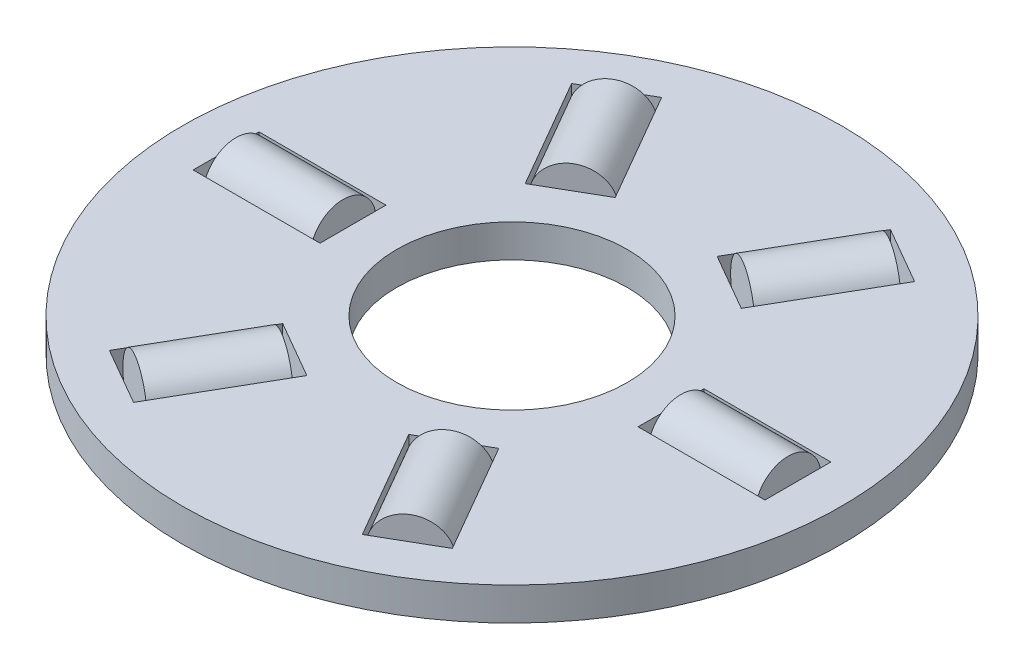
SolidWorks part; units mm, degrees
ref_plane "前视基准面" through (0, 0, 0) normal (0, 0, 1) x (1, 0, 0)
ref_plane "上视基准面" through (0, 0, 0) normal (0, 1, 0) x (1, 0, 0)
ref_plane "右视基准面" through (0, 0, 0) normal (1, 0, 0) x (0, 0, -1)
sketch "草图1" plane through (0, 0, 0) normal (0, 0, 1) x (1, 0, 0)
  line L0 (0, 87.2061) -> (0, -91.5733) construction
  line L1 (-94.3327, 0) -> (80.3525, 0) construction
  line L2 (-3.5, 0.5) -> (-3.5, -0.5)
  line L3 (-10, 0.5) -> (-3.5, 0.5)
  line L4 (-10, 0.5) -> (-10, -0.5)
  line L5 (-10, -0.5) -> (10, -0.5)
  line L6 (10, 0.5) -> (10, -0.5)
  line L7 (-8.375, 1) -> (-5.125, 1)
  line L8 (-5.125, 1) -> (-5.125, -1)
  line L9 (-5.125, -1) -> (-8.375, -1)
  line L10 (-8.375, -1) -> (-8.375, 1)
  line L11 (0, 0.5) -> (10, 0.5)
  line L12 (-6.75, 0.5) -> (-6.75, -4.4473) construction
  dimension "D1" = 1
  dimension "（Dc）" = 20
  dimension "D2" = 3.25
  dimension "dc" = 7
  dimension "Dw" = 2
sketch "草图2" plane through (0, 0, 0) normal (0, 0, 1) x (1, 0, 0)
  line L0 (-8.375, 1) -> (-5.125, 1) construction
  line L1 (-5.125, 1) -> (-5.125, -1) construction
  line L2 (-5.125, -1) -> (-8.375, -1) construction
  line L3 (-8.375, -1) -> (-8.375, 1) construction
  line L4 (-3.5, 0.5) -> (-3.5, -0.5) construction
  line L5 (-10, 0.5) -> (-3.5, 0.5) construction
  line L6 (-10, 0.5) -> (-10, -0.5) construction
  line L7 (-10, -0.5) -> (10, -0.5) construction
  line L8 (10, 0.5) -> (10, -0.5) construction
  line L9 (0, 0.5) -> (10, 0.5) construction
  line L10 (-8.375, 1) -> (-5.125, 1)
  line L11 (-5.125, 1) -> (-5.125, -1)
  line L12 (-5.125, -1) -> (-8.375, -1)
  line L13 (-8.375, -1) -> (-8.375, 1)
  line L14 (-3.5, 0.5) -> (-3.5, -0.5)
  line L15 (-10, 0.5) -> (-3.5, 0.5)
  line L16 (-10, 0.5) -> (-10, -0.5)
  line L17 (-10, -0.5) -> (10, -0.5)
  line L18 (10, 0.5) -> (10, -0.5)
  line L19 (0, 0.5) -> (10, 0.5)
  line L20 (-8.375, 0) -> (-5.125, 0)
revolve "旋转1" add sketch "草图2" angle 360 about L0 region at (-6.75, 0.25, 0) region at (-9.1875, 0, 0) region at (-4.3125, 0, 0) region at (-6.75, -0.25, 0)
sketch "草图3" plane through (0, 0, 0) normal (0, 0, 1) x (1, 0, 0)
  line L1 (-8.675, 1) -> (-4.825, 1)
  line L2 (-8.675, 1) -> (-8.675, -1)
  line L3 (-8.675, -1) -> (-4.825, -1) construction
  line L4 (-4.825, 1) -> (-4.825, -1)
  line L5 (-4.825, -1) -> (-8.675, -1)
  line L6 (-8.375, -1) -> (-8.375, 1) construction
  line L7 (-5.125, 1) -> (-5.125, -1) construction
  dimension "D1" = 0.3
  dimension "D2" = 0.3
extrude "切除-拉伸2" cut sketch "草图3" against normal mid plane 2
pattern_circular "阵列(圆周)1" count 6 over 360 about axis through (0, 87.2061, 0) along (0, 1, 0) of "切除-拉伸2"
revolve "旋转5" add sketch "草图2<6>" angle 360 about L1 region at (-6.75, 0.75, 0) region at (-6.75, 0.25, 0)
sketch "草图2<6>" plane through (0, 0, 0) normal (0, 0, 1) x (1, 0, 0) same geometry as "草图2"
pattern_circular "阵列(圆周)2" count 6 over 360 about axis through (0, 87.2061, 0) along (0, 1, 0) of bodies 102
equation "\"D1@草图1\" = \"Dw@草图1\" / 2"
equation "\"D2@草图1\" =  ( \"（Dc）@草图1\" - \"dc@草图1\" )  / 4"
equation "\"D1@切除-拉伸2\" = \"Dw@草图1\""
equation "\"D1@阵列(圆周)1\" =  int( \"（Dc）@草图1\"*0.2 ) +2"
equation "\"D1@阵列(圆周)2\" = \"D1@阵列(圆周)1\""
